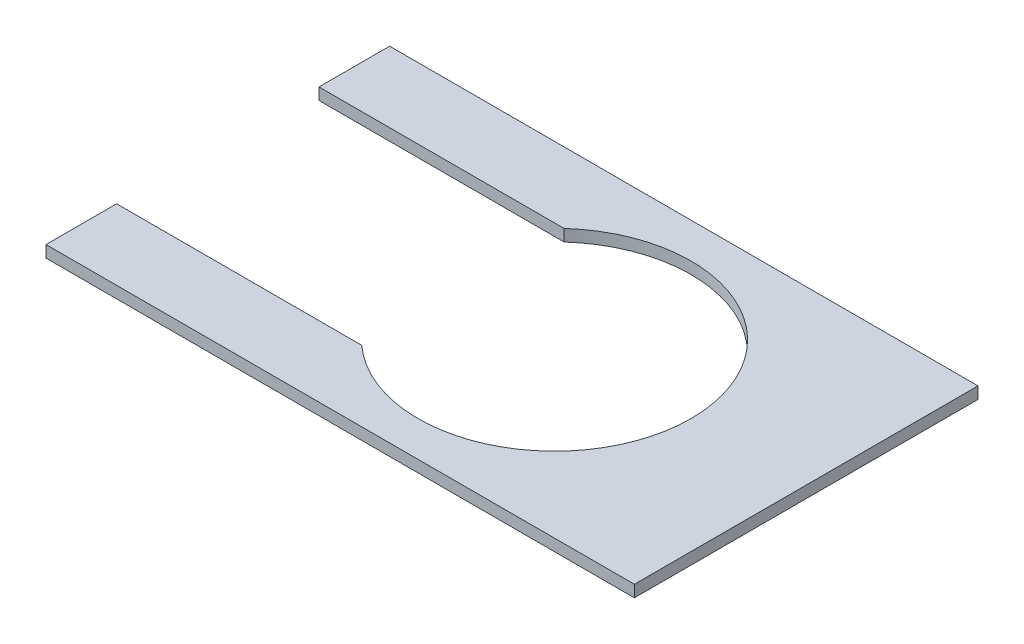
SolidWorks part; units mm, degrees
ref_plane "Front Plane" through (0, 0, 0) normal (0, 0, 1) x (1, 0, 0)
ref_plane "Top Plane" through (0, 0, 0) normal (0, 1, 0) x (1, 0, 0)
ref_plane "Right Plane" through (0, 0, 0) normal (1, 0, 0) x (0, 0, -1)
sketch "Sketch1" plane through (0, 0, 0) normal (0, 1, 0) x (1, 0, 0)
  line L0 (-118.6638, 10) -> (-118.6638, -20) construction
  line L5 (-228.6638, 10) -> (-118.6638, 10)
  line L6 (-228.6638, 10) -> (-228.6638, -20)
  line L7 (-228.6638, -20) -> (-124.5174, -20)
  line L11 (-118.6638, 10) -> (21.3362, 10)
  line L12 (21.3362, -106) -> (21.3362, 10)
  line L13 (-118.6638, -20) -> (-118.6638, -106) construction
  line L14 (-118.6638, -63) -> (-88.6227, -63) construction
  line L24 (-183.6227, -20) -> (-183.6227, -106) construction
  line L26 (21.3362, -106) -> (21.3362, -136)
  line L28 (-118.6638, -136) -> (21.3362, -136)
  line L29 (-228.6638, -136) -> (-118.6638, -136)
  line L30 (-228.6638, -136) -> (-228.6638, -106)
  line L31 (-228.6638, -106) -> (-124.5174, -106)
  line L34 (-73.6638, -20) -> (-73.6638, -106) construction
  arc A2 (-158.108, -20) -> (-209.1375, -20) centre (-183.6227, -63) ccw construction
  arc A6 (-124.5174, -106) -> (-124.5174, -20) centre (-85.5944, -63) ccw
  circle A7 centre (-183.6227, -63) radius 43 construction
  circle A8 centre (-183.6227, -63) radius 61.8136 construction
  point P24 (-183.6227, -63)
  dimension "D7" = 116
  dimension "D1" = 110
  dimension "D2" = 30
  dimension "D3" = 86
  dimension "D5" = 140
extrude "Boss-Extrude1" add sketch "Sketch1" along normal blind 5
